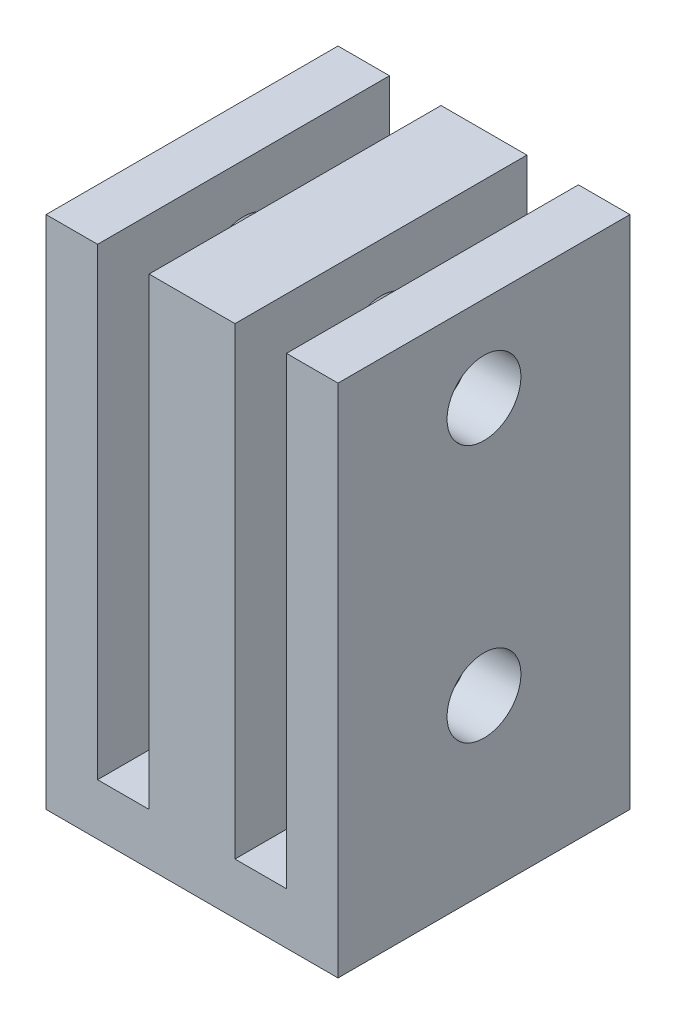
SolidWorks part; units mm, degrees
ref_plane "Front Plane" through (0, 0, 0) normal (0, 0, 1) x (1, 0, 0)
ref_plane "Top Plane" through (0, 0, 0) normal (0, 1, 0) x (1, 0, 0)
ref_plane "Right Plane" through (0, 0, 0) normal (1, 0, 0) x (0, 0, -1)
sketch "Sketch1" plane through (0, 0, 0) normal (0, 1, 0) x (1, 0, 0)
  line L1 (0, 0) -> (17, 0)
  line L2 (0, 0) -> (0, 17)
  line L3 (0, 17) -> (17, 17)
  line L4 (17, 0) -> (17, 17)
  dimension "D1" = 17
extrude "Boss-Extrude1" add sketch "Sketch1" along normal blind 30
sketch "Sketch2" plane through (0, 0, 0) normal (0, 0, 1) x (1, 0, 0)
  line L0 (0, 30) -> (17, 30) construction
  line L1 (3, 30) -> (6, 30)
  line L2 (3, 30) -> (3, 3)
  line L3 (3, 3) -> (6, 3)
  line L4 (6, 30) -> (6, 3)
  line L6 (11, 30) -> (14, 30)
  line L7 (11, 30) -> (11, 3)
  line L8 (11, 3) -> (14, 3)
  line L9 (14, 30) -> (14, 3)
  line L10 (0, 30) -> (0, 0) construction
  line L11 (0, 0) -> (17, 0) construction
  dimension "D1" = 5
  dimension "D2" = 3
  dimension "D3" = 3
  dimension "D4" = 3
extrude "Cut-Extrude1" cut sketch "Sketch2" against normal through all
sketch "Sketch3" plane through (0, 0, 0) normal (-1, 0, 0) x (0, 0, 1)
  line L0 (0, 30) -> (0, 0) construction
  line L2 (-17, 0) -> (0, 0) construction
  circle A0 centre (-8.5, 25) radius 2.15
  circle A1 centre (-8.5, 10) radius 2.15
  dimension "D1" = 4.3
  dimension "D2" = 8.5
  dimension "D3" = 15
  dimension "D4" = 10
extrude "Cut-Extrude2" cut sketch "Sketch3" against normal through all
